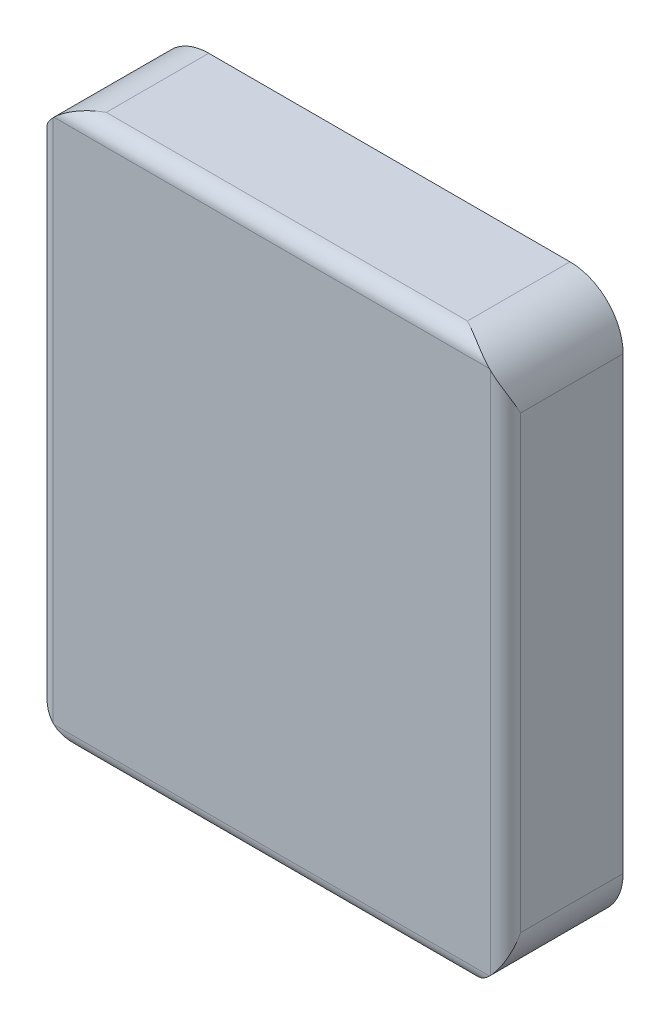
SolidWorks part; units mm, degrees
ref_plane "Front Plane" through (0, 0, 0) normal (0, 0, 1) x (1, 0, 0)
ref_plane "Top Plane" through (0, 0, 0) normal (0, 1, 0) x (1, 0, 0)
ref_plane "Right Plane" through (0, 0, 0) normal (1, 0, 0) x (0, 0, -1)
ref_plane "Plane1" through (0, 0, 0.5) normal (0, 0, -1) x (-1, 0, 0)
sketch "Sketch1" plane through (0, 0, 0.5) normal (0, 0, -1) x (-1, 0, 0)
  line L0 (-53.9, 18.5) -> (-53.9, -54.8)
  line L1 (-53.9, -54.8) -> (7.7, -54.8)
  line L2 (7.7, -54.8) -> (7.7, 18.5)
  line L3 (7.7, 18.5) -> (-53.9, 18.5)
extrude "Boss-Extrude1" add sketch "Sketch1" against normal blind 15.5
sketch "Sketch2" plane through (0, 0, 0.5) normal (0, 0, -1) x (-1, 0, 0)
  line L0 (-52.372, 16.972) -> (6.172, 16.972)
  line L1 (6.172, 16.972) -> (6.172, -53.272)
  line L2 (6.172, -53.272) -> (-52.372, -53.272)
  line L3 (-52.372, -53.272) -> (-52.372, 16.972)
extrude "Boss-Extrude2" add sketch "Sketch2" along normal blind 1
sketch "Sketch3" plane through (0, 0, -0.5) normal (0, 0, -1) x (-1, 0, 0)
  line L0 (-51.772, 16.372) -> (-51.772, -35.7342)
  line L1 (-51.772, -35.7342) -> (-49.5299, -35.7342)
  line L2 (-49.5299, -35.7342) -> (-49.5299, -51.9012)
  line L3 (-46.9, -52.672) -> (0.7, -52.672)
  line L4 (3.3299, -51.9012) -> (3.3299, -35.7342)
  line L5 (3.3299, -35.7342) -> (5.572, -35.7342)
  line L6 (5.572, -35.7342) -> (5.572, 16.372)
  line L7 (5.572, 16.372) -> (-51.772, 16.372)
  arc A0 (-49.5299, -51.9012) -> (-46.9, -52.672) centre (-46.9, -47.8) ccw
  arc A1 (0.7, -52.672) -> (3.3299, -51.9012) centre (0.7, -47.8) ccw
extrude "Cut-Extrude1" cut sketch "Sketch3" against normal blind 1
sketch "Sketch4" plane through (0, 0, 0.5) normal (0, 0, -1) x (-1, 0, 0)
  line L0 (3, -14.8) -> (4.7, -14.8)
  line L1 (4.7, -14.8) -> (4.7, 15.5)
  line L2 (4.7, 15.5) -> (-50.9, 15.5)
  line L3 (-50.9, 15.5) -> (-50.9, -14.8)
  line L4 (-50.9, -14.8) -> (-49.2, -14.8)
  line L5 (-49.2, -14.8) -> (-49.2, -31.8)
  line L6 (-49.2, -31.8) -> (-45.2, -31.8)
  line L7 (-45.2, -31.8) -> (-45.2, -50.2)
  line L8 (-45.2, -50.2) -> (-1, -50.2)
  line L9 (-1, -50.2) -> (-1, -31.8)
  line L10 (-1, -31.8) -> (3, -31.8)
  line L11 (3, -31.8) -> (3, -14.8)
extrude "Cut-Extrude2" cut sketch "Sketch4" against normal blind 5.5
sketch "Sketch5" plane through (0, 0, 6) normal (0, 0, -1) x (-1, 0, 0)
  line L0 (3, -12.7) -> (-1, -12.7)
  line L1 (-1, -12.7) -> (-1, -11.5)
  line L2 (-1, -11.5) -> (4.7, -11.5)
  line L3 (4.7, -11.5) -> (4.7, 15.5)
  line L4 (4.7, 15.5) -> (-50.9, 15.5)
  line L5 (-50.9, 15.5) -> (-50.9, -11.5)
  line L6 (-50.9, -11.5) -> (-45.2, -11.5)
  line L7 (-45.2, -11.5) -> (-45.2, -12.7)
  line L8 (-45.2, -12.7) -> (-49.2, -12.7)
  line L9 (-49.2, -12.7) -> (-49.2, -31.8)
  line L10 (-49.2, -31.8) -> (-45.2, -31.8)
  line L11 (-45.2, -31.8) -> (-45.2, -50.2)
  line L12 (-45.2, -50.2) -> (-1, -50.2)
  line L13 (-1, -50.2) -> (-1, -31.8)
  line L14 (-1, -31.8) -> (3, -31.8)
  line L15 (3, -31.8) -> (3, -12.7)
extrude "Cut-Extrude3" cut sketch "Sketch5" against normal blind 8
sketch "Sketch6" plane through (0, 0, 0.5) normal (0, 0, -1) x (-1, 0, 0)
  line L0 (-46.3, -50.2) -> (-45.2, -50.2)
  line L1 (-45.2, -50.2) -> (-45.2, -31.8)
  line L2 (-45.2, -31.8) -> (-46.3, -31.8)
  line L3 (-46.3, -31.8) -> (-46.3, -50.2)
extrude "Cut-Extrude4" cut sketch "Sketch6" against normal blind 9.3
sketch "Sketch7" plane through (0, 0, 0.5) normal (0, 0, -1) x (-1, 0, 0)
  line L0 (0.1, -31.8) -> (-1, -31.8)
  line L1 (-1, -31.8) -> (-1, -50.2)
  line L2 (-1, -50.2) -> (0.1, -50.2)
  line L3 (0.1, -50.2) -> (0.1, -31.8)
extrude "Cut-Extrude5" cut sketch "Sketch7" against normal blind 9.3
hole_wizard "Ø2.2 (2.2) Diameter Hole1" positions "Sketch9" profile "Sketch8" hole size "Ø2.2" standard "ANSI Metric"
sketch "Sketch9" plane through (-0.1, 0, 0) normal (1, 0, 0) x (0, 0, -1)
  point P0 (-5, -41.2)
sketch "Sketch8" plane through (-0.1, -41.2, 5) normal (0, 1, 0) x (0, 0, -1)
  line L0 (0, 0) -> (0, 7.6)
  line L1 (0, 7.6) -> (1.1, 7.6)
  line L2 (1.1, 7.6) -> (1.1, 0)
  line L5 (1.1, 0) -> (0, 0)
  line L11 (0, -6.35) -> (0, 107.95) construction
  dimension "Thru Hole Dia." = 2.2
  dimension "Thru Hole Depth" = 7.6
fillet "Fillet1" radius 2 6 edges at (53.9, -18.15, 16) (23.1, 18.5, 16) (23.1, -54.8, 16) (-7.7, -18.15, 16) (50.9, 15.5, 7.25) (-4.7, 15.5, 7.25) tangent propagation no
fillet "Fillet2" radius 4.872 2 edges at (-5.572, 16.372, 0) (51.772, 16.372, 0) tangent propagation no
fillet "Fillet3" radius 5.472 4 edges at (52.372, -53.272, 0) (52.372, 16.972, 0) (-6.172, -53.272, 0) (-6.172, 16.972, 0) tangent propagation no
fillet "Fillet4" radius 7 4 edges at (-7.7, -54.8, 7.25) (-7.7, 18.5, 7.25) (53.9, 18.5, 7.25) (53.9, -54.8, 7.25) tangent propagation no
